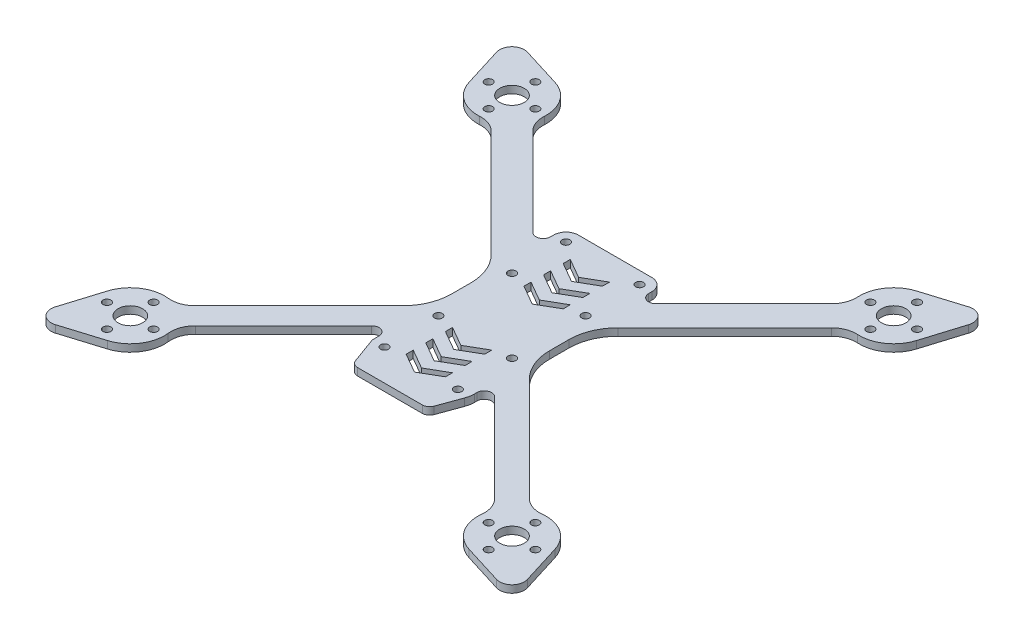
SolidWorks part; units mm, degrees
ref_plane "Front Plane" through (0, 0, 0) normal (0, 0, 1) x (1, 0, 0)
ref_plane "Top Plane" through (0, 0, 0) normal (0, 1, 0) x (1, 0, 0)
ref_plane "Right Plane" through (0, 0, 0) normal (1, 0, 0) x (0, 0, -1)
sketch "Sketch1" plane through (0, 0, 0) normal (0, 1, 0) x (1, 0, 0)
  line L0 (0, 110) -> (0, -110) construction
  line L3 (19.341, -38.6569) -> (16.0219, -47.7761)
  line L4 (-15, 42) -> (15, 42)
  line L7 (20, 3.2304) -> (20, -4.6447)
  line L8 (-15, 15) -> (15, 15) construction
  line L10 (-15, -15) -> (15, -15) construction
  line L11 (15, 15) -> (15, -15) construction
  line L12 (25.1213, 33.6066) -> (60.89, 69.3753)
  line L13 (25.8579, 17.3726) -> (69.3753, 60.89)
  line L14 (25.0654, -32.1365) -> (60.9986, -68.0696)
  line L15 (25.8579, -18.7868) -> (68.0696, -60.9986)
  line L16 (77.7817, 77.7817) -> (98.9949, 98.9949) construction
  line L17 (77.7817, -77.7817) -> (98.9949, -98.9949) construction
  line L18 (73.6461, -91.157) -> (89.9418, -96.1957)
  line L19 (96.1957, -89.9418) -> (91.157, -73.6461)
  line L20 (89.9418, 96.1957) -> (73.6461, 91.157)
  line L21 (96.1957, 89.9418) -> (91.157, 73.6461)
  line L22 (0, 0) -> (77.7817, 77.7817) construction
  line L23 (20, 37) -> (20, 35.7279)
  line L24 (0, 0) -> (77.7817, -77.7817) construction
  line L35 (-20, 0) -> (20, 0) construction
  line L37 (19.9441, -34.2578) -> (19.9441, -35.2367)
  line L38 (-19.9441, -37) -> (-16.0219, -47.7761)
  line L39 (0, 0) -> (-77.7817, -77.7817) construction
  line L40 (0, 0) -> (-77.7817, 77.7817) construction
  line L41 (-77.7817, -77.7817) -> (-98.9949, -98.9949) construction
  line L42 (-77.7817, 77.7817) -> (-98.9949, 98.9949) construction
  line L43 (-15, 15) -> (-15, -15) construction
  line L46 (-19.9441, -34.2578) -> (-19.9441, -37)
  line L47 (-20, 37) -> (-20, 35.7279)
  line L48 (-96.1957, 89.9418) -> (-91.157, 73.6461)
  line L49 (-89.9418, 96.1957) -> (-73.6461, 91.157)
  line L50 (-96.1957, -89.9418) -> (-91.157, -73.6461)
  line L51 (-73.6461, -91.157) -> (-89.9418, -96.1957)
  line L52 (-25.8579, -18.7868) -> (-68.0696, -60.9986)
  line L53 (-25.0654, -32.1365) -> (-60.9986, -68.0696)
  line L54 (-25.8579, 17.3726) -> (-69.3753, 60.89)
  line L55 (-25.1213, 33.6066) -> (-60.89, 69.3753)
  line L56 (-20, 3.2304) -> (-20, -4.6447)
  line L59 (-13.2028, -49.75) -> (13.2028, -49.75)
  circle A1 centre (77.7817, 77.7817) radius 63.5 construction
  circle A2 centre (77.7817, -77.7817) radius 63.5 construction
  circle A5 centre (77.7817, 77.7817) radius 9.5 construction
  circle A9 centre (77.7817, 68.2817) radius 1.6
  circle A10 centre (68.2817, 77.7817) radius 1.6
  circle A11 centre (77.7817, 87.2817) radius 1.6
  circle A12 centre (87.2817, 77.7817) radius 1.6
  circle A13 centre (77.7817, -87.2817) radius 1.6
  circle A14 centre (77.7817, -77.7817) radius 9.5 construction
  circle A15 centre (68.2817, -77.7817) radius 1.6
  circle A16 centre (77.7817, -68.2817) radius 1.6
  circle A17 centre (87.2817, -77.7817) radius 1.6
  arc A28 (77.0028, 63.8034) -> (91.157, 73.6461) centre (77.7817, 77.7817) ccw
  arc A29 (63.8668, -76.2411) -> (73.6461, -91.157) centre (77.7817, -77.7817) ccw
  arc A30 (73.6461, 91.157) -> (63.8034, 77.0028) centre (77.7817, 77.7817) ccw
  arc A31 (91.157, -73.6461) -> (76.2411, -63.8668) centre (77.7817, -77.7817) ccw
  arc A36 (96.1957, 89.9418) -> (89.9418, 96.1957) centre (91.4188, 91.4188) ccw
  arc A37 (96.1957, -89.9418) -> (89.9418, -96.1957) centre (91.4188, -91.4188) cw
  circle A42 centre (15, 15) radius 1.6
  circle A43 centre (15, -15) radius 1.6
  circle A44 centre (77.7817, 77.7817) radius 5
  circle A45 centre (77.7817, -77.7817) radius 5
  circle A47 centre (0, 0) radius 110 construction
  circle A49 centre (-87.2817, -77.7817) radius 1.6 [skipped]
  circle A50 centre (-77.7817, -68.2817) radius 1.6 [skipped]
  circle A51 centre (-68.2817, -77.7817) radius 1.6 [skipped]
  circle A52 centre (-77.7817, -87.2817) radius 1.6 [skipped]
  circle A53 centre (-77.7817, 87.2817) radius 1.6 [skipped]
  circle A54 centre (-68.2817, 77.7817) radius 1.6 [skipped]
  circle A55 centre (-77.7817, 68.2817) radius 1.6 [skipped]
  circle A56 centre (-87.2817, 77.7817) radius 1.6 [skipped]
  circle A57 centre (-77.7817, -77.7817) radius 9.5 construction
  circle A58 centre (-77.7817, 77.7817) radius 9.5 construction
  circle A91 centre (14.9441, -37) radius 1.6
  circle A92 centre (15, 37) radius 1.6
  arc A97 (60.89, 69.3753) -> (63.8034, 77.0028) centre (53.8189, 76.4463) ccw
  arc A98 (69.3753, 60.89) -> (77.0028, 63.8034) centre (76.4463, 53.8189) cw
  arc A99 (63.8668, -76.2411) -> (60.9986, -68.0696) centre (53.9275, -75.1407) ccw
  arc A100 (68.0696, -60.9986) -> (76.2411, -63.8668) centre (75.1407, -53.9275) ccw
  circle A103 centre (-77.7817, -77.7817) radius 9.5 construction
  circle A104 centre (-77.7817, 77.7817) radius 9.5 construction
  circle A105 centre (-77.7817, -77.7817) radius 63.5 construction
  circle A106 centre (-77.7817, 77.7817) radius 63.5 construction
  arc A107 (-68.0696, -60.9986) -> (-76.2411, -63.8668) centre (-75.1407, -53.9275) cw
  arc A108 (-63.8668, -76.2411) -> (-60.9986, -68.0696) centre (-53.9275, -75.1407) cw
  arc A109 (-69.3753, 60.89) -> (-77.0028, 63.8034) centre (-76.4463, 53.8189) ccw
  arc A110 (-60.89, 69.3753) -> (-63.8034, 77.0028) centre (-53.8189, 76.4463) cw
  circle A111 centre (-15, 37) radius 1.6
  circle A112 centre (-14.9441, -37) radius 1.6
  circle A113 centre (-77.7817, -77.7817) radius 5
  circle A114 centre (-77.7817, 77.7817) radius 5
  circle A115 centre (-15, -15) radius 1.6
  circle A116 centre (-15, 15) radius 1.6
  arc A117 (-96.1957, -89.9418) -> (-89.9418, -96.1957) centre (-91.4188, -91.4188) ccw
  arc A118 (-96.1957, 89.9418) -> (-89.9418, 96.1957) centre (-91.4188, 91.4188) cw
  arc A119 (-91.157, -73.6461) -> (-76.2411, -63.8668) centre (-77.7817, -77.7817) cw
  arc A120 (-73.6461, 91.157) -> (-63.8034, 77.0028) centre (-77.7817, 77.7817) cw
  arc A121 (-63.8668, -76.2411) -> (-73.6461, -91.157) centre (-77.7817, -77.7817) cw
  arc A122 (-77.0028, 63.8034) -> (-91.157, 73.6461) centre (-77.7817, 77.7817) cw
  circle A123 centre (-87.2817, -77.7817) radius 1.6
  circle A124 centre (-77.7817, -68.2817) radius 1.6
  circle A125 centre (-68.2817, -77.7817) radius 1.6
  circle A126 centre (-77.7817, -87.2817) radius 1.6
  circle A127 centre (-87.2817, 77.7817) radius 1.6
  circle A128 centre (-77.7817, 87.2817) radius 1.6
  circle A129 centre (-68.2817, 77.7817) radius 1.6
  circle A130 centre (-77.7817, 68.2817) radius 1.6
  arc A131 (20, 35.7279) -> (25.1213, 33.6066) centre (23, 35.7279) ccw
  arc A132 (25.0654, -32.1365) -> (19.9441, -34.2578) centre (22.9441, -34.2578) ccw
  arc A133 (-25.8579, -18.7868) -> (-20, -4.6447) centre (-40, -4.6447) ccw
  arc A134 (-25.8579, 17.3726) -> (-20, 3.2304) centre (-40, 3.2304) cw
  arc A135 (25.8579, -18.7868) -> (20, -4.6447) centre (40, -4.6447) cw
  arc A136 (25.8579, 17.3726) -> (20, 3.2304) centre (40, 3.2304) ccw
  arc A137 (-19.9441, -34.2578) -> (-25.0654, -32.1365) centre (-22.9441, -34.2578) ccw
  arc A138 (-20, 35.7279) -> (-25.1213, 33.6066) centre (-23, 35.7279) cw
  arc A141 (15, 42) -> (20, 37) centre (15, 37) cw
  arc A142 (-20, 37) -> (-15, 42) centre (-15, 37) cw
  arc A143 (-16.0219, -47.7761) -> (-13.2028, -49.75) centre (-13.2028, -46.75) ccw
  arc A144 (13.2028, -49.75) -> (16.0219, -47.7761) centre (13.2028, -46.75) ccw
  arc A145 (19.9441, -35.2367) -> (19.341, -38.6569) centre (9.9441, -35.2367) cw
  point P4 (0, 15)
  point P6 (0, 15)
  point P12 (0, 38)
  point P34 (77.7817, 77.7817)
  point P49 (0, -15)
  point P50 (0, 15)
  point P65 (0, 0)
  point P75 (-77.7817, 77.7817)
  point P76 (0, 42)
  point P80 (0, -15)
  point P89 (0, 38)
  point P93 (0, -15)
  point P160 (0, -38)
  point P165 (0, -42)
  point P168 (20, 28.4853)
  point P171 (19.9441, -27.0152)
  point P178 (-20, -12.9289)
  point P180 (0, -38)
  point P182 (-20, 11.5147)
  point P185 (20, -12.9289)
  point P188 (20, 11.5147)
  point P190 (-19.9441, -27.0152)
  point P193 (-20, 28.4853)
  point P196 (-19.9441, -42)
  point P199 (19.9441, -42)
  point P202 (20, 42)
  point P205 (-20, 42)
  dimension "D3" = 42
  dimension "D9" = 4
  dimension "D13" = 20
  dimension "D17" = 10
  dimension "D18" = 5
  dimension "D19" = 12.75
  dimension "D5" = 5
  dimension "D6" = 5
  dimension "D7" = 6
  dimension "D8" = 6
  dimension "D11" = 3
  dimension "D12" = 10
  dimension "D14" = 3
  dimension "D4" = 3
  dimension "D2" = 20
  dimension "D15" = 30
  dimension "D16" = 30
  dimension "D10" = 4
extrude "Boss-Extrude1" add sketch "Sketch1" along normal blind 3
sketch "Sketch2" plane through (0, 0, 0) normal (0, -1, 0) x (1, 0, 0)
  line L0 (0, -42) -> (0, 49.75) construction
  line L1 (15, -42) -> (-15, -42) construction
  line L2 (-13.2028, 49.75) -> (13.2028, 49.75) construction
  line L3 (-8, 35.1312) -> (0, 39.75)
  line L4 (0, 39.75) -> (8, 35.1312)
  line L6 (8, 32.2444) -> (0, 36.8632)
  line L7 (0, 36.8632) -> (-8, 32.2444)
  line L8 (-8, 32.2444) -> (-8, 35.1312)
  line L9 (8, 32.2444) -> (8, 35.1312)
  line L10 (-8, 27.1312) -> (0, 31.75)
  line L11 (0, 31.75) -> (8, 27.1312)
  line L12 (8, 24.2444) -> (0, 28.8632)
  line L13 (0, 28.8632) -> (-8, 24.2444)
  line L14 (-8, 24.2444) -> (-8, 27.1312)
  line L15 (8, 24.2444) -> (8, 27.1312)
  line L16 (-8, 19.1312) -> (0, 23.75)
  line L17 (0, 23.75) -> (8, 19.1312)
  line L18 (8, 16.2444) -> (0, 20.8632)
  line L19 (0, 20.8632) -> (-8, 16.2444)
  line L20 (-8, 16.2444) -> (-8, 19.1312)
  line L21 (8, 16.2444) -> (8, 19.1312)
  line L40 (-8, -12.8688) -> (0, -8.25)
  line L41 (0, -8.25) -> (8, -12.8688)
  line L42 (8, -15.7556) -> (0, -11.1368)
  line L43 (0, -11.1368) -> (-8, -15.7556)
  line L44 (-8, -15.7556) -> (-8, -12.8688)
  line L45 (8, -15.7556) -> (8, -12.8688)
  line L46 (-8, -20.8688) -> (0, -16.25)
  line L47 (0, -16.25) -> (8, -20.8688)
  line L48 (8, -23.7556) -> (0, -19.1368)
  line L49 (0, -19.1368) -> (-8, -23.7556)
  line L50 (-8, -23.7556) -> (-8, -20.8688)
  line L51 (8, -23.7556) -> (8, -20.8688)
  line L52 (-8, -28.8688) -> (0, -24.25)
  line L53 (0, -24.25) -> (8, -28.8688)
  line L54 (8, -31.7556) -> (0, -27.1368)
  line L55 (0, -27.1368) -> (-8, -31.7556)
  line L56 (-8, -31.7556) -> (-8, -28.8688)
  line L57 (8, -31.7556) -> (8, -28.8688)
  line L58 (-8, 11.1312) -> (0, 15.75) [skipped]
  line L59 (0, 15.75) -> (8, 11.1312) [skipped]
  line L60 (8, 8.2444) -> (0, 12.8632) [skipped]
  line L61 (0, 12.8632) -> (-8, 8.2444) [skipped]
  line L62 (-8, 8.2444) -> (-8, 11.1312) [skipped]
  line L63 (8, 8.2444) -> (8, 11.1312) [skipped]
  line L64 (-8, 3.1312) -> (0, 7.75) [skipped]
  line L65 (0, 7.75) -> (8, 3.1312) [skipped]
  line L66 (8, 0.2444) -> (0, 4.8632) [skipped]
  line L67 (0, 4.8632) -> (-8, 0.2444) [skipped]
  line L68 (-8, 0.2444) -> (-8, 3.1312) [skipped]
  line L69 (8, 0.2444) -> (8, 3.1312) [skipped]
  line L70 (-8, -4.8688) -> (0, -0.25) [skipped]
  line L71 (0, -0.25) -> (8, -4.8688) [skipped]
  line L72 (0, -3.1368) -> (-8, -7.7556) [skipped]
  line L73 (8, -7.7556) -> (0, -3.1368) [skipped]
  line L74 (-8, -7.7556) -> (-8, -4.8688) [skipped]
  line L75 (8, -7.7556) -> (8, -4.8688) [skipped]
  dimension "D1" = 8
  dimension "D2" = 8
  dimension "D3" = 2.5
  dimension "D4" = 10
  dimension "D5" = 120
  dimension "D6" = 60
  dimension "D7" = 9
extrude "Cut-Extrude1" cut sketch "Sketch2" against normal through all
